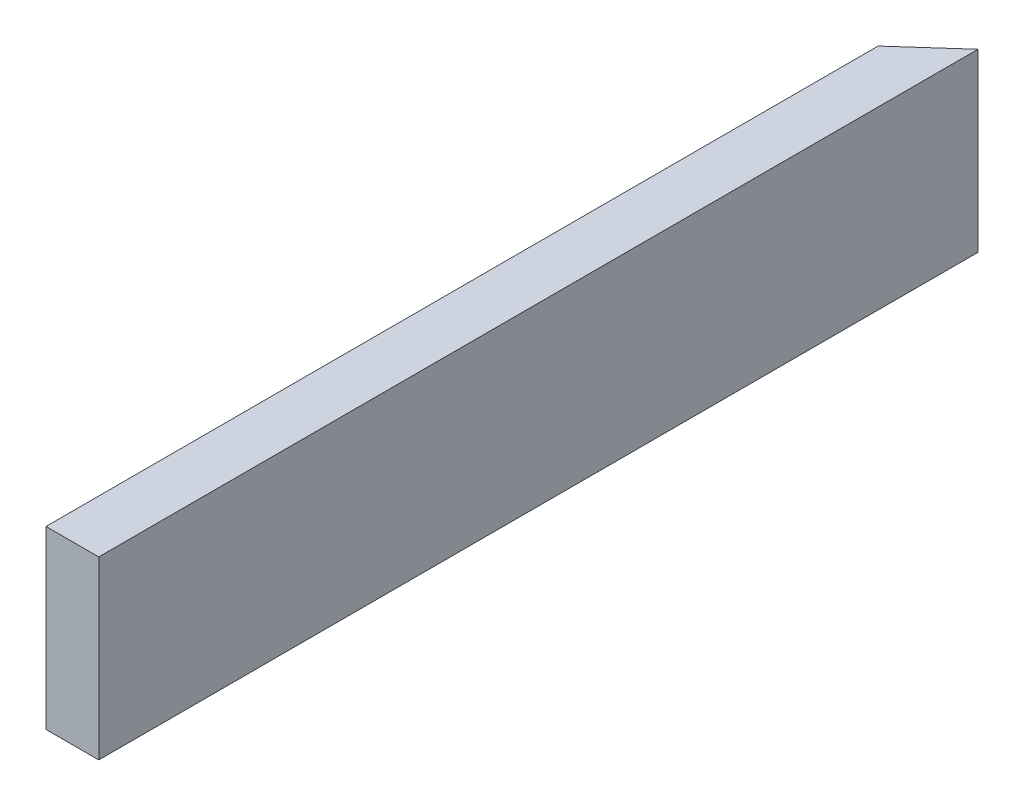
SolidWorks part; units mm, degrees
ref_plane "Front Plane" through (0, 0, 0) normal (0, 0, 1) x (1, 0, 0)
ref_plane "Top Plane" through (0, 0, 0) normal (0, 1, 0) x (1, 0, 0)
ref_plane "Right Plane" through (0, 0, 0) normal (1, 0, 0) x (0, 0, -1)
sketch "Sketch1" plane through (0, 0, 0) normal (0, 0, 1) x (1, 0, 0)
  line L1 (-3.9032, 12.8387) -> (-0.9032, 12.8387)
  line L2 (-3.9032, 12.8387) -> (-3.9032, 2.8387)
  line L3 (-3.9032, 2.8387) -> (-0.9032, 2.8387)
  line L4 (-0.9032, 12.8387) -> (-0.9032, 2.8387)
  dimension "D1" = 3
  dimension "D2" = 10
extrude "Boss-Extrude1" add sketch "Sketch1" along normal blind 50
ref_plane "Plane1" through (0, 12.8387, 0) normal (0, 1, 0) x (1, 0, 0)
sketch "Sketch3" plane through (0, 12.8387, 0) normal (0, 1, 0) x (1, 0, 0)
  line L0 (-0.9032, 0) -> (-3.9032, -2.6823)
  line L1 (-3.9032, -50) -> (-3.9032, 0) construction
  line L2 (-3.9032, -2.6823) -> (-3.9032, 0)
  line L3 (-3.9032, 0) -> (-0.9032, 0)
  dimension "D1" = 41.8
extrude "Cut-Extrude1" cut sketch "Sketch3" against normal blind 52
